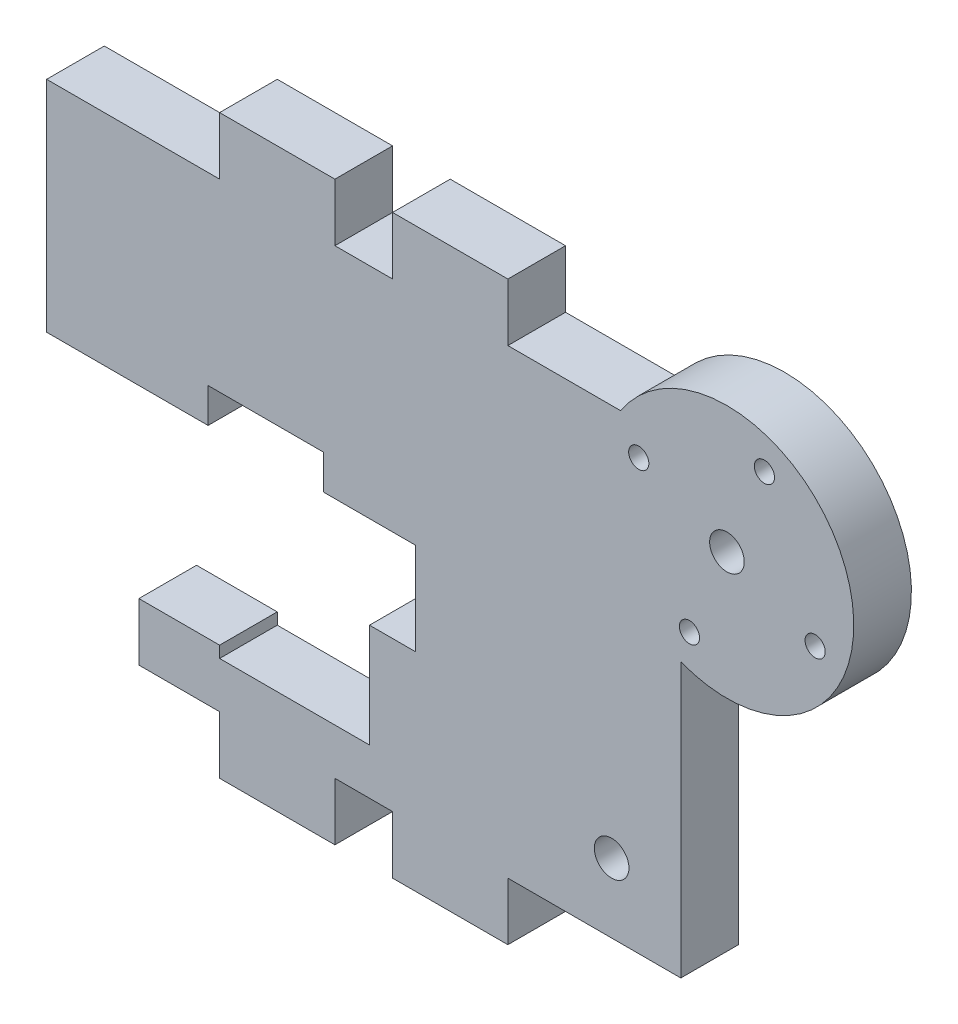
SolidWorks part; units mm, degrees
ref_plane "Plan de face" through (0, 0, 0) normal (0, 0, 1) x (1, 0, 0)
ref_plane "Plan de dessus" through (0, 0, 0) normal (0, 1, 0) x (1, 0, 0)
ref_plane "Plan de droite" through (0, 0, 0) normal (1, 0, 0) x (0, 0, -1)
sketch "Esquisse1" plane through (0, 0, 0) normal (0, 0, 1) x (1, 0, 0)
  line L0 (-1, 20) -> (50, 20) construction
  line L1 (10, 0) -> (15, 0)
  line L2 (0, 5) -> (0, 4)
  line L3 (10, 40) -> (15, 40)
  line L5 (25, 40) -> (34.7805, 40)
  line L6 (0, 40) -> (0, 45)
  line L7 (0, 45) -> (10, 45)
  line L8 (10, 40) -> (10, 45)
  line L9 (25, 0) -> (40, 0)
  line L10 (15, 40) -> (15, 45)
  line L11 (15, 45) -> (25, 45)
  line L12 (25, 40) -> (25, 45)
  line L13 (25, 0) -> (25, -5)
  line L14 (15, -5) -> (25, -5)
  line L15 (15, 0) -> (15, -5)
  line L16 (10, 0) -> (10, -5)
  line L17 (0, -5) -> (10, -5)
  line L18 (0, 0) -> (0, -5)
  line L19 (-1, 20) -> (-1, 24)
  line L20 (0, 4) -> (13, 4)
  line L21 (44, 34) -> (36.35, 34) construction
  line L22 (-1, 24) -> (9, 24)
  line L23 (17, 13) -> (17, 21)
  line L24 (0, 0) -> (-7, 0)
  line L25 (0, 0) -> (0, 5)
  line L26 (0, 5) -> (-7, 5)
  line L27 (-7, 0) -> (-7, 5)
  line L28 (0, 40) -> (-15, 40)
  line L29 (0, 40) -> (0, 21)
  line L30 (0, 21) -> (-15, 21)
  line L31 (-15, 40) -> (-15, 21)
  line L32 (17, 21) -> (9, 21)
  line L33 (36.35, 34) -> (36.35, 37.25) construction
  line L35 (9, 21) -> (9, 24)
  line L36 (17, 13) -> (13, 13)
  line L38 (40, 0) -> (40, 23.753)
  line L39 (13, 13) -> (13, 4)
  circle A0 centre (34, 6) radius 1.5
  circle A1 centre (44, 34) radius 1.5
  arc A2 (40, 23.753) -> (34.7805, 40) centre (44, 34) ccw
  circle A3 centre (36.35, 34) radius 0.875 construction
  circle A4 centre (36.35, 37.25) radius 0.875
  circle A5 centre (47.25, 41.65) radius 0.875
  circle A6 centre (51.65, 30.75) radius 0.875
  circle A7 centre (40.75, 26.35) radius 0.875
  point P56 (44, 34)
  dimension "D18" = 15
  dimension "D19" = 3
  dimension "D25" = 3.25
  dimension "D27" = 11
  dimension "D28" = 1.75
  dimension "D1" = 40
  dimension "D3" = 10
  dimension "D4" = 5
  dimension "D5" = 5
  dimension "D6" = 5
  dimension "D7" = 7
  dimension "D8" = 15
  dimension "D9" = 19
  dimension "D10" = 10
  dimension "D11" = 4
  dimension "D12" = 4
  dimension "D13" = 4
  dimension "D14" = 3
  dimension "D15" = 8
  dimension "D16" = 4
  dimension "D17" = 8
  dimension "D20" = 6
  dimension "D21" = 6
  dimension "D22" = 23
  dimension "D23" = 6
  dimension "D26" = 7.65
  dimension "D29" = 4
extrude "Boss.-Extru.1" add sketch "Esquisse1" along normal blind 5 contours L29 L0 L5 L12 L11 L10 L3 L8 L7 L6 | L28 L31 L30 L29 | L0 L19 L22 L23 L20 L2 L25 L18 L17 L16 L1 L15 L14 L13 L9 | L27 L24 L25 L26 region at (25.1234, 23.1957, 0) region at (-3.5, 2.5, 0) region at (-7.5745, 30.5851, 0)
